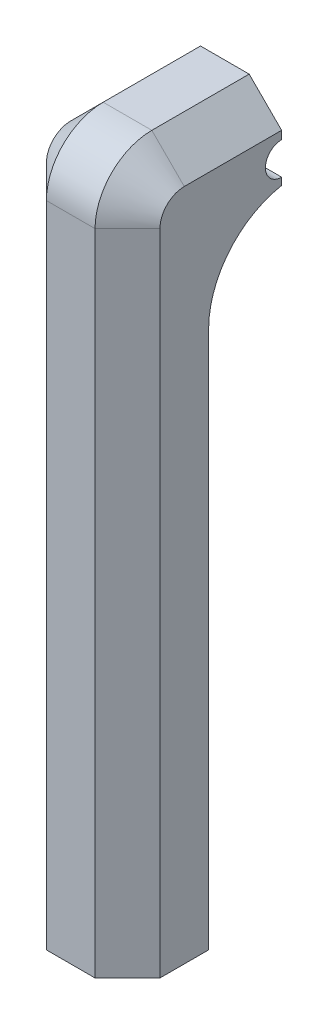
SolidWorks part; units mm, degrees
ref_plane "Ön Düzlem" through (0, 0, 0) normal (0, 0, 1) x (1, 0, 0)
ref_plane "Üst Düzlem" through (0, 0, 0) normal (0, 1, 0) x (1, 0, 0)
ref_plane "Sağ Düzlem" through (0, 0, 0) normal (1, 0, 0) x (0, 0, -1)
sketch "Çizim3" plane through (0, 0, 0) normal (1, 0, 0) x (0, 0, -1)
  line L2 (17.5, 182.5) -> (17.5, 0)
  line L3 (17.5, 0) -> (-17.5, 0)
  line L4 (-17.5, 0) -> (-17.5, 217.5)
  line L5 (-17.5, 217.5) -> (30, 217.5)
  line L6 (30, 217.5) -> (30, 182.5)
  line L7 (30, 182.5) -> (17.5, 182.5)
extrude "Yükseklik-Ekstrüzyon4" add sketch "Çizim3" along normal blind 35
fillet "Radyus1" radius 17.5 1 edges at (17.5, 217.5, 17.5)
fillet "Radyus2" radius 17.5 1 edges at (17.5, 182.5, -17.5)
sketch "Çizim4" plane through (35, 0, 0) normal (1, 0, 0) x (0, 0, -1)
  line L0 (30, 182.5) -> (30, 217.5) construction
  circle A0 centre (30, 200) radius 5
  dimension "D1" = 10
extrude "Kes-Ekstrüzyon1" cut sketch "Çizim4" against normal through all
chamfer "Pah1" distance 10 angle 45 3 edges at (0, 100, 17.5) (0, 212.3744, 12.3744) (0, 217.5, -15)
chamfer "Pah2" distance 10 angle 45 3 edges at (35, 100, 17.5) (35, 212.3744, 12.3744) (35, 217.5, -15)
chamfer "Pah4" distance 10 angle 45 2 edges at (35, 82.8647, -17.5) (35, 176.1877, -20.9688)
chamfer "Pah5" distance 10 angle 45 2 edges at (0, 82.8647, -17.5) (0, 176.1877, -20.9688)
